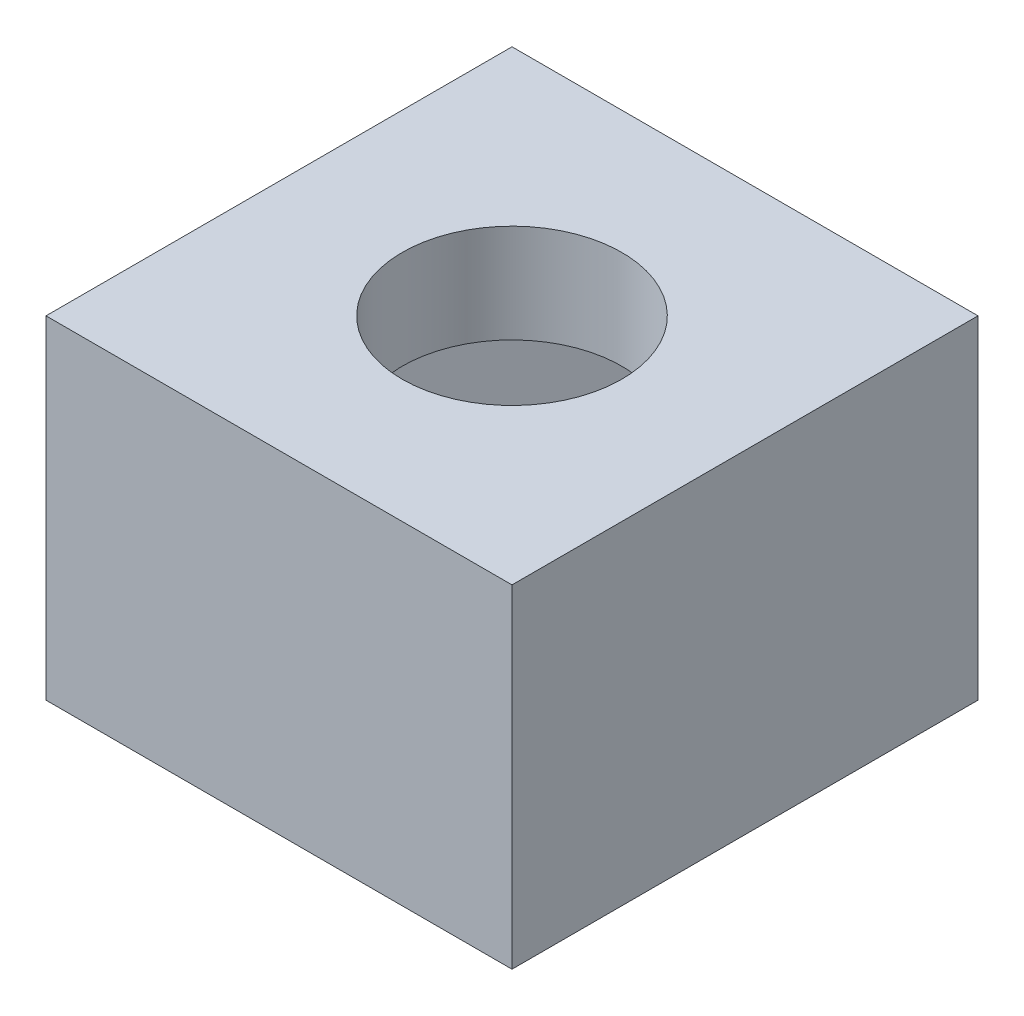
SolidWorks part; units mm, degrees
ref_plane "Front Plane" through (0, 0, 0) normal (0, 0, 1) x (1, 0, 0)
ref_plane "Top Plane" through (0, 0, 0) normal (0, 1, 0) x (1, 0, 0)
ref_plane "Right Plane" through (0, 0, 0) normal (1, 0, 0) x (0, 0, -1)
sketch "Sketch1" plane through (0, 0, 0) normal (0, 1, 0) x (1, 0, 0)
  line L1 (-4.1778, 1.3717) -> (2.8222, 1.3717)
  line L2 (-4.1778, 1.3717) -> (-4.1778, -5.6283)
  line L3 (-4.1778, -5.6283) -> (2.8222, -5.6283)
  line L4 (2.8222, 1.3717) -> (2.8222, -5.6283)
  dimension "D1" = 7
  dimension "D2" = 7
extrude "Boss-Extrude1" add sketch "Sketch1" along normal blind 5
sketch "Sketch4" plane through (0, 5, 0) normal (0, 1, 0) x (1, 0, 0)
  line L1 (-1.5445, 1.1062) -> (-3.9123, -1.2616)
  line L2 (-3.9123, -1.2616) -> (-3.0456, -4.4961)
  line L3 (-3.0456, -4.4961) -> (0.1889, -5.3628)
  line L4 (0.1889, -5.3628) -> (2.5567, -2.995)
  line L5 (2.5567, -2.995) -> (1.69, 0.2396)
  line L6 (1.69, 0.2396) -> (-1.5445, 1.1062)
  circle A0 centre (-0.6778, -2.1283) radius 1.65
  circle A1 centre (-0.6778, -2.1283) radius 2.9 construction
  dimension "D1" = 5.8
extrude "Cut-Extrude4" cut sketch "Sketch4" against normal blind 4
sketch "Sketch6" plane through (0, 5, 0) normal (0, 1, 0) x (1, 0, 0)
  line L1 (-3.9123, -1.2616) -> (-3.0456, -4.4961)
  line L2 (-3.0456, -4.4961) -> (0.1889, -5.3628)
  line L3 (0.1889, -5.3628) -> (2.5567, -2.995)
  line L4 (2.5567, -2.995) -> (1.69, 0.2396)
  line L5 (1.69, 0.2396) -> (-1.5445, 1.1062)
  line L6 (-1.5445, 1.1062) -> (-3.9123, -1.2616)
  circle A0 centre (-0.6778, -2.1283) radius 1.65
  circle A1 centre (-0.6778, -2.1283) radius 2.9 construction
  circle A2 centre (-0.6778, -2.1283) radius 1.65
  circle M2 centre (-0.6778, -2.1283) radius 1.65
  dimension "D1" = 5.8
extrude "Cut-Extrude6" cut sketch "Sketch6" against normal blind 4 contours M2 region at (-0.6778, 5, 2.1283)
extrude "Boss-Extrude2" add sketch "Sketch6<4>" against normal blind 1.48 contours L5 L6 L1 L2 L3 L4 M2 region at (-2.6637, 5, 0.1424)
sketch "Sketch6<4>" plane through (0, 5, 0) normal (0, 1, 0) x (1, 0, 0) same geometry as "Sketch6"
